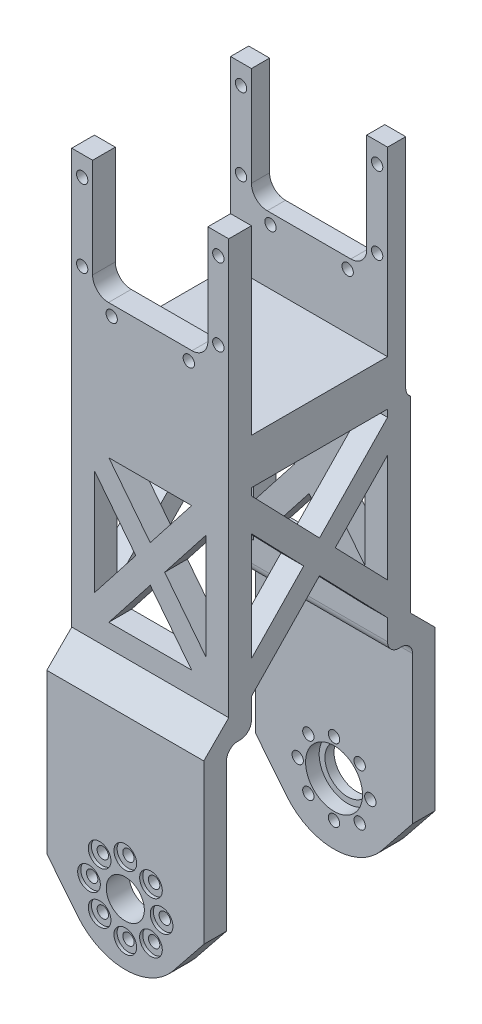
SolidWorks part; units mm, degrees
ref_plane "Front Plane" through (0, 0, 0) normal (0, 0, 1) x (1, 0, 0)
ref_plane "Top Plane" through (0, 0, 0) normal (0, 1, 0) x (1, 0, 0)
ref_plane "Right Plane" through (0, 0, 0) normal (1, 0, 0) x (0, 0, -1)
sketch "Sketch2" plane through (0, 0, 0) normal (0, 0, 1) x (1, 0, 0)
  line L2 (0, 0) -> (-9.2, 0)
  line L3 (-12.2, 3) -> (-12.2, 42)
  line L4 (-10.8583, 44.5) -> (-11.3127, 44.5)
  line L5 (-13.2175, 43.6191) -> (-16.7048, 39.5164)
  line L6 (-17.3, 37.8973) -> (-17.3, 1.5027)
  line L7 (-16.7048, -0.1164) -> (-13.2175, -4.2191)
  line L8 (-11.3127, -5.1) -> (0, -5.1)
  line L12 (0, 0) -> (0, -5.1)
  line L13 (-17.3, 24.9) -> (-12.2, 24.9)
  circle A2 centre (-15, 37.5) radius 1.25
  circle A3 centre (-15, 20.5) radius 1.25
  circle A4 centre (-15, 3.5) radius 1.25
  arc A8 (-12.2, 3) -> (-9.2, 0) centre (-9.2, 3) ccw
  arc A9 (-10.8583, 44.5) -> (-12.2, 42) centre (-9.2, 42) ccw
  arc A10 (-11.3127, 44.5) -> (-13.2175, 43.6191) centre (-11.3127, 42) ccw
  arc A11 (-16.7048, 39.5164) -> (-17.3, 37.8973) centre (-14.8, 37.8973) ccw
  arc A12 (-17.3, 1.5027) -> (-16.7048, -0.1164) centre (-14.8, 1.5027) ccw
  arc A13 (-13.2175, -4.2191) -> (-11.3127, -5.1) centre (-11.3127, -2.6) ccw
  circle A17 centre (-8.5, -2.8) radius 1.25
  dimension "D1" = 2.5
  dimension "D2" = 3
  dimension "D3" = 2.5
  dimension "D4" = 8.5
  dimension "D5" = 10.8583
  dimension "D6" = 11.3127
  dimension "D7" = 13.2175
  dimension "D8" = 14.8
  dimension "D9" = 1.5027
  dimension "D10" = 15
  dimension "D11" = 3.5
  dimension "D12" = 20.5
  dimension "D13" = 37.5
  dimension "D14" = 37.8973
  dimension "D15" = 30
  dimension "D21" = 2.8
extrude "Boss-Extrude2" add sketch "Sketch2" along normal blind 5 contours L7 A13 L8 L12 L2 A8 L3 L13 L6 A12 A17 A3 A4 region at (-0.3463, -2.55, 0)
mirror "Mirror2" about plane through (0, 0, 5) normal (1, 0, 0) of "Boss-Extrude2"
sketch "Sketch3" plane through (0, 0, 5) normal (0, 0, 1) x (1, 0, 0)
  line L20 (-12.7, 24.4) -> (-12.7, 24.9)
  line L21 (12.7, 24.4) -> (12.7, 24.9)
  line L30 (-16.3239, 0.2074) -> (-12.8366, -3.8953)
  line L31 (-11.3127, -4.6) -> (11.3127, -4.6)
  line L32 (12.8366, -3.8953) -> (16.3239, 0.2074)
  line L33 (16.8, 1.5027) -> (16.8, 24.4)
  line L34 (16.8, 24.4) -> (12.7, 24.4)
  line L35 (12.7, 24.4) -> (12.7, 3)
  line L36 (9.2, -0.5) -> (-9.2, -0.5)
  line L37 (-12.7, 3) -> (-12.7, 24.4)
  line L38 (-12.7, 24.4) -> (-16.8, 24.4)
  line L39 (-16.8, 24.4) -> (-16.8, 1.5027)
  line L40 (-16.3239, 0.2074) -> (-12.8366, -3.8953)
  line L41 (-11.3127, -4.6) -> (11.3127, -4.6)
  line L42 (12.8366, -3.8953) -> (16.3239, 0.2074)
  line L43 (16.8, 1.5027) -> (16.8, 24.4)
  line L44 (16.8, 24.4) -> (12.7, 24.4)
  line L45 (12.7, 24.4) -> (12.7, 3)
  line L46 (9.2, -0.5) -> (-9.2, -0.5)
  line L47 (-12.7, 3) -> (-12.7, 24.4)
  line L48 (-12.7, 24.4) -> (-16.8, 24.4)
  line L49 (-16.8, 24.4) -> (-16.8, 1.5027)
  line L50 (-16.7048, -0.1164) -> (-13.2175, -4.2191)
  line L51 (-11.3127, -5.1) -> (11.3127, -5.1)
  line L52 (13.2175, -4.2191) -> (16.7048, -0.1164)
  line L53 (17.3, 1.5027) -> (17.3, 24.9)
  line L54 (17.3, 24.9) -> (12.2, 24.9)
  line L55 (12.2, 24.9) -> (12.2, 3)
  line L56 (9.2, 0) -> (-9.2, 0)
  line L57 (-12.2, 3) -> (-12.2, 24.9)
  line L58 (-12.2, 24.9) -> (-17.3, 24.9)
  line L59 (-17.3, 24.9) -> (-17.3, 1.5027)
  line L60 (-16.7048, -0.1164) -> (-13.2175, -4.2191)
  line L61 (-11.3127, -5.1) -> (11.3127, -5.1)
  line L62 (13.2175, -4.2191) -> (16.7048, -0.1164)
  line L63 (17.3, 1.5027) -> (17.3, 24.9)
  line L64 (17.3, 24.9) -> (12.2, 24.9)
  line L65 (12.2, 24.9) -> (12.2, 3)
  line L66 (9.2, 0) -> (-9.2, 0)
  line L67 (-12.2, 3) -> (-12.2, 24.9)
  line L68 (-12.2, 24.9) -> (-17.3, 24.9)
  line L69 (-17.3, 24.9) -> (-17.3, 1.5027)
  arc A18 (-12.8366, -3.8953) -> (-11.3127, -4.6) centre (-11.3127, -2.6) ccw
  arc A19 (11.3127, -4.6) -> (12.8366, -3.8953) centre (11.3127, -2.6) ccw
  arc A20 (16.3239, 0.2074) -> (16.8, 1.5027) centre (14.8, 1.5027) ccw
  arc A21 (9.2, -0.5) -> (12.7, 3) centre (9.2, 3) ccw
  arc A22 (-12.7, 3) -> (-9.2, -0.5) centre (-9.2, 3) ccw
  arc A23 (-16.8, 1.5027) -> (-16.3239, 0.2074) centre (-14.8, 1.5027) ccw
  arc A24 (-12.8366, -3.8953) -> (-11.3127, -4.6) centre (-11.3127, -2.6) ccw
  arc A25 (11.3127, -4.6) -> (12.8366, -3.8953) centre (11.3127, -2.6) ccw
  arc A26 (16.3239, 0.2074) -> (16.8, 1.5027) centre (14.8, 1.5027) ccw
  arc A27 (9.2, -0.5) -> (12.7, 3) centre (9.2, 3) ccw
  arc A28 (-12.7, 3) -> (-9.2, -0.5) centre (-9.2, 3) ccw
  arc A29 (-16.8, 1.5027) -> (-16.3239, 0.2074) centre (-14.8, 1.5027) ccw
  arc A30 (-13.2175, -4.2191) -> (-11.3127, -5.1) centre (-11.3127, -2.6) ccw
  arc A31 (11.3127, -5.1) -> (13.2175, -4.2191) centre (11.3127, -2.6) ccw
  arc A32 (16.7048, -0.1164) -> (17.3, 1.5027) centre (14.8, 1.5027) ccw
  arc A33 (9.2, 0) -> (12.2, 3) centre (9.2, 3) ccw
  arc A34 (-12.2, 3) -> (-9.2, 0) centre (-9.2, 3) ccw
  arc A35 (-17.3, 1.5027) -> (-16.7048, -0.1164) centre (-14.8, 1.5027) ccw
  arc A36 (-13.2175, -4.2191) -> (-11.3127, -5.1) centre (-11.3127, -2.6) ccw
  arc A37 (11.3127, -5.1) -> (13.2175, -4.2191) centre (11.3127, -2.6) ccw
  arc A38 (16.7048, -0.1164) -> (17.3, 1.5027) centre (14.8, 1.5027) ccw
  arc A39 (9.2, 0) -> (12.2, 3) centre (9.2, 3) ccw
  arc A40 (-12.2, 3) -> (-9.2, 0) centre (-9.2, 3) ccw
  arc A41 (-17.3, 1.5027) -> (-16.7048, -0.1164) centre (-14.8, 1.5027) ccw
  line M43 (17.3, 24.9) -> (12.2, 24.9)
  line M44 (12.2, 24.9) -> (12.2, 3)
  arc M45 (12.2, 3) -> (9.2, 0) centre (9.2, 3) cw
  line M46 (9.2, 0) -> (-9.2, 0)
  arc M47 (-9.2, 0) -> (-12.2, 3) centre (-9.2, 3) cw
  line M48 (-12.2, 3) -> (-12.2, 24.9)
  line M49 (-12.2, 24.9) -> (-17.3, 24.9)
  dimension "D1" = 0.5
  dimension "D2" = 0
extrude "Cut-Extrude1" cut sketch "Sketch3" against normal blind 7.5 contours L47 A28 L46 A27 L45 L21 L20 M43 M44 M45 M46 M47 M48 M49 region at (-12.3408, 24.65, 5)
sketch "Sketch4" plane through (0, 0, 5) normal (0, 0, 1) x (1, 0, 0)
  line L0 (-17.3, 1.5027) -> (-17.3, -25.1)
  line L1 (-17.3, -25.1) -> (17.3, -25.1)
  line L2 (17.3, -25.1) -> (17.3, 1.5027)
  line L10 (-12.7, 3) -> (-12.7, 24.9)
  line L11 (-12.7, 24.9) -> (-17.3, 24.9)
  line L12 (-17.3, 24.9) -> (-17.3, 1.5027)
  line L13 (-16.7048, -0.1164) -> (-13.2175, -4.2191)
  line L14 (-11.3127, -5.1) -> (11.3127, -5.1)
  line L15 (13.2175, -4.2191) -> (16.7048, -0.1164)
  line L16 (17.3, 1.5027) -> (17.3, 24.9)
  line L17 (17.3, 24.9) -> (12.7, 24.9)
  line L18 (12.7, 24.9) -> (12.7, 3)
  line L19 (9.2, -0.5) -> (-9.2, -0.5)
  line L20 (-12.7, 3) -> (-12.7, 24.9)
  line L21 (-12.7, 24.9) -> (-17.3, 24.9)
  line L22 (-17.3, 24.9) -> (-17.3, 1.5027)
  line L23 (-16.7048, -0.1164) -> (-13.2175, -4.2191)
  line L24 (-11.3127, -5.1) -> (11.3127, -5.1)
  line L25 (13.2175, -4.2191) -> (16.7048, -0.1164)
  line L26 (17.3, 1.5027) -> (17.3, 24.9)
  line L27 (17.3, 24.9) -> (12.7, 24.9)
  line L28 (12.7, 24.9) -> (12.7, 3)
  line L29 (9.2, -0.5) -> (-9.2, -0.5)
  arc A6 (-12.7, 3) -> (-9.2, -0.5) centre (-9.2, 3) ccw
  arc A7 (-17.3, 1.5027) -> (-16.7048, -0.1164) centre (-14.8, 1.5027) ccw
  arc A8 (-13.2175, -4.2191) -> (-11.3127, -5.1) centre (-11.3127, -2.6) ccw
  arc A9 (11.3127, -5.1) -> (13.2175, -4.2191) centre (11.3127, -2.6) ccw
  arc A10 (16.7048, -0.1164) -> (17.3, 1.5027) centre (14.8, 1.5027) ccw
  arc A11 (9.2, -0.5) -> (12.7, 3) centre (9.2, 3) ccw
  arc A12 (-12.7, 3) -> (-9.2, -0.5) centre (-9.2, 3) ccw
  arc A13 (-17.3, 1.5027) -> (-16.7048, -0.1164) centre (-14.8, 1.5027) ccw
  arc A14 (-13.2175, -4.2191) -> (-11.3127, -5.1) centre (-11.3127, -2.6) ccw
  arc A15 (11.3127, -5.1) -> (13.2175, -4.2191) centre (11.3127, -2.6) ccw
  arc A16 (16.7048, -0.1164) -> (17.3, 1.5027) centre (14.8, 1.5027) ccw
  arc A17 (9.2, -0.5) -> (12.7, 3) centre (9.2, 3) ccw
  arc M29 (-17.3, 1.5027) -> (-16.7048, -0.1164) centre (-14.8, 1.5027) ccw
  line M30 (-16.7048, -0.1164) -> (-13.2175, -4.2191)
  arc M31 (-13.2175, -4.2191) -> (-11.3127, -5.1) centre (-11.3127, -2.6) ccw
  line M32 (-11.3127, -5.1) -> (11.3127, -5.1)
  arc M33 (11.3127, -5.1) -> (13.2175, -4.2191) centre (11.3127, -2.6) ccw
  line M34 (13.2175, -4.2191) -> (16.7048, -0.1164)
  arc M35 (16.7048, -0.1164) -> (17.3, 1.5027) centre (14.8, 1.5027) ccw
  dimension "D2" = 20
  dimension "D1" = 0
extrude "Boss-Extrude3" add sketch "Sketch4" against normal up to surface (5 mm away) contours L1 L2 L0 M35 M34 M33 M32 M31 M30 M29 region at (0, -14.637, 5) up to face at (13.75, 3.5, 0)
ref_plane "Plane1" through (0, 0, -15) normal (0, 0, -1) x (-1, 0, 0)
sketch "Sketch5" plane through (0, 0, 0) normal (0, 0, -1) x (-1, 0, 0)
  line L0 (-17.3, 24.9) -> (-17.3, -25.1) construction
  line L1 (17.3, -25.1) -> (-17.3, -25.1)
  line L2 (17.3, -25.1) -> (17.3, -15.1)
  line L3 (17.3, -15.1) -> (-17.3, -15.1)
  line L4 (-17.3, -25.1) -> (-17.3, -15.1)
  dimension "D1" = 10
extrude "Boss-Extrude4" add sketch "Sketch5" along normal up to surface (15 mm away) up to plane "Plane1"
mirror "Mirror4" about plane through (0, 0, -15) normal (0, 0, -1) of "Boss-Extrude4"
sketch "Sketch6" plane through (0, 0, -30) normal (0, 0, -1) x (-1, 0, 0)
  line L0 (-17.3, -15.1) -> (-17.3, -25.1)
  line L1 (-17.3, -25.1) -> (17.3, -25.1)
  line L2 (17.3, -25.1) -> (17.3, -15.1)
  line L8 (-17.3, -15.1) -> (17.3, -15.1)
  line L9 (17.3, -15.1) -> (17.3, 24.9)
  line L10 (17.3, 24.9) -> (12.7, 24.9)
  line L11 (12.7, 24.9) -> (12.7, 3)
  line L12 (9.2, -0.5) -> (-9.2, -0.5)
  line L13 (-12.7, 3) -> (-12.7, 24.9)
  line L14 (-12.7, 24.9) -> (-17.3, 24.9)
  line L15 (-17.3, 24.9) -> (-17.3, -15.1)
  line L16 (-17.3, -15.1) -> (17.3, -15.1)
  line L17 (17.3, -15.1) -> (17.3, 24.9)
  line L18 (17.3, 24.9) -> (12.7, 24.9)
  line L19 (12.7, 24.9) -> (12.7, 3)
  line L20 (9.2, -0.5) -> (-9.2, -0.5)
  line L21 (-12.7, 3) -> (-12.7, 24.9)
  line L22 (-12.7, 24.9) -> (-17.3, 24.9)
  line L23 (-17.3, 24.9) -> (-17.3, -15.1)
  circle A1 centre (8.5, -2.8) radius 1.25
  circle A2 centre (8.5, -2.8) radius 1.25
  circle A3 centre (15, 20.5) radius 1.25
  circle A4 centre (15, 20.5) radius 1.25
  circle A5 centre (15, 3.5) radius 1.25
  circle A6 centre (15, 3.5) radius 1.25
  circle A7 centre (-8.5, -2.8) radius 1.25
  circle A8 centre (-8.5, -2.8) radius 1.25
  circle A9 centre (-15, 20.5) radius 1.25
  circle A10 centre (-15, 20.5) radius 1.25
  circle A11 centre (-15, 3.5) radius 1.25
  circle A12 centre (-15, 3.5) radius 1.25
  arc A14 (9.2, -0.5) -> (12.7, 3) centre (9.2, 3) ccw
  arc A15 (-12.7, 3) -> (-9.2, -0.5) centre (-9.2, 3) ccw
  arc A16 (9.2, -0.5) -> (12.7, 3) centre (9.2, 3) ccw
  arc A17 (-12.7, 3) -> (-9.2, -0.5) centre (-9.2, 3) ccw
  line M17 (17.3, -25.1) -> (17.3, -15.1)
  line M18 (17.3, -15.1) -> (-17.3, -15.1)
  line M19 (-17.3, -15.1) -> (-17.3, -25.1)
  line M20 (-17.3, -25.1) -> (17.3, -25.1)
  dimension "D1" = 0
  dimension "D2" = 0
  dimension "D3" = 0
  dimension "D4" = 0
  dimension "D5" = 0
  dimension "D6" = 0
  dimension "D7" = 0
extrude "Boss-Extrude5" add sketch "Sketch6" along normal blind 4 contours A17 L21 L22 L23 L17 L18 L19 A16 L20 A12 A10 A8 A6 A4 A2 M18 | M20 M17 M18 M19 region at (0, -20.1, -30) region at (0, -1.8135, -30)
sketch "Sketch7" plane through (0, 0, 5) normal (0, 0, 1) x (1, 0, 0)
  line L0 (-17.3, -25.1) -> (-17.3, -107)
  line L1 (-12.7, 3) -> (-12.7, 24.9) construction
  line L3 (17.3, -107) -> (17.3, -25.1)
  line L4 (-17.3, -25.1) -> (17.3, -25.1) construction
  line L5 (17.3, 24.9) -> (17.3, -25.1) construction
  line L6 (-17.3, -25.1) -> (17.3, -25.1)
  line L8 (-10.5347, -115.4422) -> (-17.3, -107)
  line L9 (17.3, -107) -> (10.5347, -115.4422)
  circle A0 centre (8, -107) radius 1.25
  circle A1 centre (0, -115) radius 1.25
  circle A2 centre (-8, -107) radius 1.25
  circle A3 centre (5.6569, -112.6569) radius 1.25
  circle A4 centre (-5.6569, -112.6569) radius 1.25
  circle A5 centre (5.6569, -101.3431) radius 1.25
  circle A6 centre (-5.6569, -101.3431) radius 1.25
  circle A7 centre (0, -99) radius 1.25
  circle A8 centre (0, -107) radius 4.2
  circle A9 centre (0, -107) radius 13.5
  point P28 (0, -107)
  line M18 (-17.3, -25.1) -> (17.3, -25.1)
  dimension "D2" = 8.4
  dimension "D3" = 27
  dimension "D4" = 2.5
  dimension "D5" = 4.7
  dimension "D6" = 7.0431
  dimension "D7" = 18.3569
  dimension "D8" = 20.7
  dimension "D9" = 123.9
  dimension "D10" = 126.2431
  dimension "D11" = 137.5569
  dimension "D12" = 139.9
  dimension "D13" = 106.5
extrude "Boss-Extrude6" add sketch "Sketch7" against normal blind 5 contours A9 L9 L3 L0 L8 M18 | A9 A0 A1 A2 A3 A4 A5 A6 A7 A8 region at (0, -62.5123, 5) region at (-4.3474, -94.6231, 5)
mirror "Mirror7" about plane through (0, 0, -15) normal (0, 0, -1) of "Boss-Extrude6"
sketch "Sketch8" plane through (0, 0, -35) normal (0, 0, -1) x (-1, 0, 0)
  line L5 (10.5347, -115.4422) -> (17.3, -107)
  line L6 (17.3, -107) -> (17.3, -25.1)
  line L7 (17.3, -25.1) -> (-17.3, -25.1)
  line L8 (-17.3, -25.1) -> (-17.3, -107)
  line L9 (-17.3, -107) -> (-10.5347, -115.4422)
  line L10 (10.5347, -115.4422) -> (17.3, -107)
  line L11 (17.3, -107) -> (17.3, -25.1)
  line L12 (17.3, -25.1) -> (-17.3, -25.1)
  line L13 (-17.3, -25.1) -> (-17.3, -107)
  line L14 (-17.3, -107) -> (-10.5347, -115.4422)
  arc A1 (-10.5347, -115.4422) -> (10.5347, -115.4422) centre (0, -107) ccw
  arc A2 (-10.5347, -115.4422) -> (10.5347, -115.4422) centre (0, -107) ccw
  dimension "D1" = 0
extrude "Boss-Extrude7" add sketch "Sketch7<5>" along normal blind 5.5 contours A9 A0 A1 A2 A3 A4 A5 A6 A7 A8 region at (-4.3474, -94.6231, 5)
sketch "Sketch7<5>" plane through (0, 0, 5) normal (0, 0, 1) x (1, 0, 0) same geometry as "Sketch7"
sketch "Sketch9" plane through (0, 0, 5) normal (0, 0, 1) x (1, 0, 0)
  line L0 (-17.3, -72) -> (17.3, -72)
  line L1 (-17.3, 24.9) -> (-17.3, -107) construction
  line L2 (17.3, 24.9) -> (17.3, -107) construction
  line L12 (10.5347, -115.4422) -> (17.3, -107)
  line L13 (17.3, -107) -> (17.3, 24.9)
  line L14 (17.3, 24.9) -> (12.7, 24.9)
  line L15 (12.7, 24.9) -> (12.7, 3)
  line L16 (9.2, -0.5) -> (-9.2, -0.5)
  line L17 (-12.7, 3) -> (-12.7, 24.9)
  line L18 (-12.7, 24.9) -> (-17.3, 24.9)
  line L19 (-17.3, 24.9) -> (-17.3, -107)
  line L20 (-17.3, -107) -> (-10.5347, -115.4422)
  line L21 (10.5347, -115.4422) -> (17.3, -107)
  line L22 (17.3, -107) -> (17.3, 24.9)
  line L23 (17.3, 24.9) -> (12.7, 24.9)
  line L24 (12.7, 24.9) -> (12.7, 3)
  line L25 (9.2, -0.5) -> (-9.2, -0.5)
  line L26 (-12.7, 3) -> (-12.7, 24.9)
  line L27 (-12.7, 24.9) -> (-17.3, 24.9)
  line L28 (-17.3, 24.9) -> (-17.3, -107)
  line L29 (-17.3, -107) -> (-10.5347, -115.4422)
  arc A3 (10.5347, -115.4422) -> (-10.5347, -115.4422) centre (0, -107) ccw
  arc A4 (9.2, -0.5) -> (12.7, 3) centre (9.2, 3) ccw
  arc A5 (-12.7, 3) -> (-9.2, -0.5) centre (-9.2, 3) ccw
  arc A6 (10.5347, -115.4422) -> (-10.5347, -115.4422) centre (0, -107) ccw
  arc A7 (9.2, -0.5) -> (12.7, 3) centre (9.2, 3) ccw
  arc A8 (-12.7, 3) -> (-9.2, -0.5) centre (-9.2, 3) ccw
  arc M14 (-10.5347, -115.4422) -> (10.5347, -115.4422) centre (0, -107) cw
  line M15 (10.5347, -115.4422) -> (17.3, -107)
  line M16 (17.3, -107) -> (17.3, 24.9)
  line M24 (-17.3, 24.9) -> (-17.3, -107)
  line M25 (-17.3, -107) -> (-10.5347, -115.4422)
  dimension "D2" = 35
  dimension "D1" = 0
extrude "Boss-Extrude8" add sketch "Sketch9" along normal blind 5.5 contours L0 M24 M25 M14 M15 M16 region at (0, -86.4211, 5)
chamfer "Chamfer1" distance 5.5 angle 45 1 edges at (0, -72, 5)
sketch "Sketch10" plane through (0, 0, 0) normal (0, 0, -1) x (-1, 0, 0)
  line L0 (-17.3, -72) -> (17.3, -72)
  line L1 (-17.3, -107) -> (-17.3, -25.1) construction
  line L2 (17.3, -25.1) -> (17.3, -107) construction
  line L8 (10.5347, -115.4422) -> (17.3, -107)
  line L9 (17.3, -107) -> (17.3, -25.1)
  line L10 (17.3, -25.1) -> (-17.3, -25.1)
  line L11 (-17.3, -25.1) -> (-17.3, -107)
  line L12 (-17.3, -107) -> (-10.5347, -115.4422)
  line L13 (10.5347, -115.4422) -> (17.3, -107)
  line L14 (17.3, -107) -> (17.3, -25.1)
  line L15 (17.3, -25.1) -> (-17.3, -25.1)
  line L16 (-17.3, -25.1) -> (-17.3, -107)
  line L17 (-17.3, -107) -> (-10.5347, -115.4422)
  circle A0 centre (0, -107) radius 4.2 construction
  arc A2 (-10.5347, -115.4422) -> (10.5347, -115.4422) centre (0, -107) ccw
  arc A3 (-10.5347, -115.4422) -> (10.5347, -115.4422) centre (0, -107) ccw
  line M8 (10.5347, -115.4422) -> (17.3, -107)
  line M9 (17.3, -107) -> (17.3, -25.1)
  line M11 (-17.3, -25.1) -> (-17.3, -107)
  line M12 (-17.3, -107) -> (-10.5347, -115.4422)
  arc M13 (-10.5347, -115.4422) -> (10.5347, -115.4422) centre (0, -107) ccw
  circle M14 centre (-8, -107) radius 1.25
  circle M15 centre (0, -115) radius 1.25
  circle M16 centre (8, -107) radius 1.25
  circle M17 centre (-5.6569, -112.6569) radius 1.25
  circle M18 centre (5.6569, -112.6569) radius 1.25
  circle M19 centre (-5.6569, -101.3431) radius 1.25
  circle M20 centre (5.6569, -101.3431) radius 1.25
  circle M21 centre (0, -99) radius 1.25
  circle M22 centre (0, -107) radius 4.2
  dimension "D1" = 35
  dimension "D2" = 0
extrude "Cut-Extrude3" cut sketch "Sketch10" against normal blind 5.5 contours L0 M11 M12 M13 M8 M9 M14 M16 M18 M20 M22 M21 M19 M17 M15 region at (0, -93.3197, 0)
fillet "Fillet1" radius 2.5 2 edges at (0, -72, 0) (0, -72, 5.5)
mirror "Mirror8" about plane through (0, 0, -15) normal (0, 0, -1) of "Boss-Extrude8", "Boss-Extrude7"
chamfer "Chamfer2" distance 5.5 angle 45 1 edges at (0, -72, -35)
fillet "Fillet2" radius 2.5 1 edges at (0, -25.1, -34)
mirror "Mirror9" about plane through (0, 0, -15) normal (0, 0, -1) of "Cut-Extrude3"
fillet "Fillet3" radius 2.5 2 edges at (0, -72, -30) (0, -72, -35.5)
sketch "Sketch11" plane through (0, 0, 5) normal (0, 0, 1) x (1, 0, 0)
  line L0 (17.3, 24.9) -> (17.3, -66.5) construction
  line L1 (-17.3, -66.5) -> (17.3, -66.5)
  line L2 (-17.3, -66.5) -> (-17.3, -25.1)
  line L3 (-17.3, -25.1) -> (17.3, -25.1)
  line L4 (17.3, -66.5) -> (17.3, -25.1)
  line L5 (-17.3, -25.1) -> (17.3, -25.1) construction
  line L6 (-12.3, -61.5) -> (-12.3, -30.1)
  line L7 (-12.3, -30.1) -> (12.3, -30.1)
  line L8 (12.3, -61.5) -> (12.3, -30.1)
  line L9 (-12.3, -61.5) -> (12.3, -61.5)
  line L10 (-12.3, -61.5) -> (12.3, -30.1)
  line L11 (12.3, -61.5) -> (-12.3, -30.1)
  line L12 (14.268, -59.9582) -> (-10.332, -28.5582)
  line L13 (-10.332, -63.0418) -> (14.268, -31.6418)
  line L14 (10.332, -63.0418) -> (-14.268, -31.6418)
  line L15 (-14.268, -59.9582) -> (10.332, -28.5582)
  dimension "D1" = 5
  dimension "D2" = 2.5
  dimension "D3" = 2.5
extrude "Cut-Extrude4" cut sketch "Sketch11" against normal up to surface (40 mm away) contours L6 L15 L14 | L9 L14 L13 | L12 L15 L7 | L13 L12 L8 region at (-9.2586, -45.8, 5) region at (0, -57.6179, 5) region at (0, -33.9821, 5) region at (9.2586, -45.8, 5)
sketch "Sketch12" plane through (-17.3, 0, 0) normal (-1, 0, 0) x (0, 0, 1)
  line L0 (5, 24.9) -> (5, -66.5) construction
  line L1 (-35, -66.5) -> (5, -66.5)
  line L2 (-35, -66.5) -> (-35, -25.1)
  line L3 (-35, -25.1) -> (5, -25.1)
  line L4 (5, -66.5) -> (5, -25.1)
  line L5 (-30, -25.1) -> (0, -25.1) construction
  line L6 (-35, -66.5) -> (5, -25.1)
  line L7 (5, -66.5) -> (-35, -25.1)
  line L8 (6.7979, -64.7629) -> (-33.2021, -23.3629)
  line L9 (-33.2021, -68.2371) -> (6.7979, -26.8371)
  line L10 (3.2021, -68.2371) -> (-36.7979, -26.8371)
  line L11 (-36.7979, -64.7629) -> (3.2021, -23.3629)
  line M5 (-30, -69.5) -> (-30, -25.1)
  line M7 (0, -25.1) -> (0, -69.5)
  dimension "D1" = 2.5
  dimension "D2" = 2.5
extrude "Boss-Extrude9" add sketch "Sketch12" against normal blind 5 contours L11 L6 L10 M5 | L9 L10 L6 M5 | L10 L11 L7 M5 | L7 L11 L8 M5 | L11 L10 L6 L7 | L10 L9 L7 L6 | L7 L9 L8 L6 | L11 L7 L6 L8 | L11 L8 L6 M7 | L8 L9 L6 M7 | L9 L7 L8 M7 | L10 L7 L9 M7 region at (-17.3, -53.1443, -23.7934) region at (-17.3, -55.8389, -22.9256) region at (-17.3, -45.8, -16.7381) region at (-17.3, -47.599, -15) region at (-17.3, -55.8389, -7.0744) region at (-17.3, -38.4557, -23.7934) region at (-17.3, -44.001, -15) region at (-17.3, -45.8, -13.2619) region at (-17.3, -53.1443, -6.2066) region at (-17.3, -35.7611, -22.9256) region at (-17.3, -35.7611, -7.0744) region at (-17.3, -38.4557, -6.2066)
ref_plane "Plane2" through (0, 0, 0) normal (1, 0, 0) x (0, 0, -1)
mirror "Mirror10" about plane through (0, 0, 0) normal (1, 0, 0) of "Boss-Extrude9"
sketch "Sketch15" plane through (0, 0, -35.5) normal (0, 0, 1) x (1, 0, 0)
  circle A0 centre (0, -107) radius 6.275
  dimension "D1" = 12.55
extrude "Cut-Extrude5" cut sketch "Sketch15" against normal blind 3
sketch "Sketch16" plane through (0, 0, -38.5) normal (0, 0, 1) x (1, 0, 0)
  circle A0 centre (0, -107) radius 5
  dimension "D1" = 10
extrude "Cut-Extrude6" cut sketch "Sketch16" against normal through all
sketch "Sketch17" plane through (0, 0, 10.5) normal (0, 0, 1) x (1, 0, 0)
  circle A0 centre (0, -99) radius 2.5
  dimension "D1" = 5
extrude "Cut-Extrude7" cut sketch "Sketch17" against normal blind 0.7
pattern_circular "CirPattern1" count 8 over 360 about axis through (0, -107, 0) along (0, 0, 1) of "Cut-Extrude7" reverse direction yes
ref_plane "Plane3" through (0, 0, -15) normal (0, 0, 1) x (1, 0, 0)
mirror "Mirror11" about plane through (0, 0, -15) normal (0, 0, 1) of "Cut-Extrude7", "CirPattern1"
